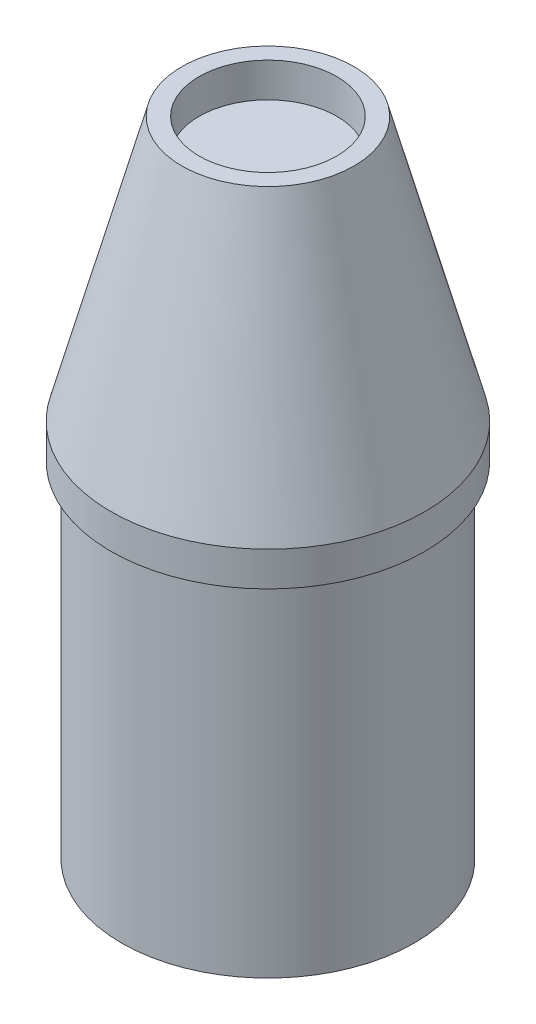
SolidWorks part; units mm, degrees
material "6061 Alloy"
ref_plane "Front Plane" through (0, 0, 0) normal (0, 0, 1) x (1, 0, 0)
ref_plane "Top Plane" through (0, 0, 0) normal (0, 1, 0) x (1, 0, 0)
ref_plane "Right Plane" through (0, 0, 0) normal (1, 0, 0) x (0, 0, -1)
sketch "Sketch1" plane through (0, 0, 0) normal (0, 0, 1) x (1, 0, 0)
  line L0 (0, -16.9497) -> (0, 95.227)
  line L1 (0, 95.227) -> (12.7, 95.227)
  line L2 (12.7, 95.227) -> (12.7, 101.577)
  line L3 (12.7, 101.577) -> (15.875, 101.577)
  line L4 (15.875, 101.577) -> (28.9179, 52.9003)
  line L5 (28.9179, 52.9003) -> (28.9179, 46.5503)
  line L6 (28.9179, 46.5503) -> (26.9875, 46.5503)
  line L7 (26.9875, 46.5503) -> (26.9875, -16.9497)
  line L8 (26.9875, -16.9497) -> (0, -16.9497)
  dimension "D1" = 28.9179
  dimension "D2" = 15
  dimension "D3" = 15.875
  dimension "D5" = 63.5
  dimension "D6" = 6.35
  dimension "D7" = 12.7
  dimension "D8" = 26.9875
revolve "Revolve1" add sketch "Sketch1" angle 360 about L0
